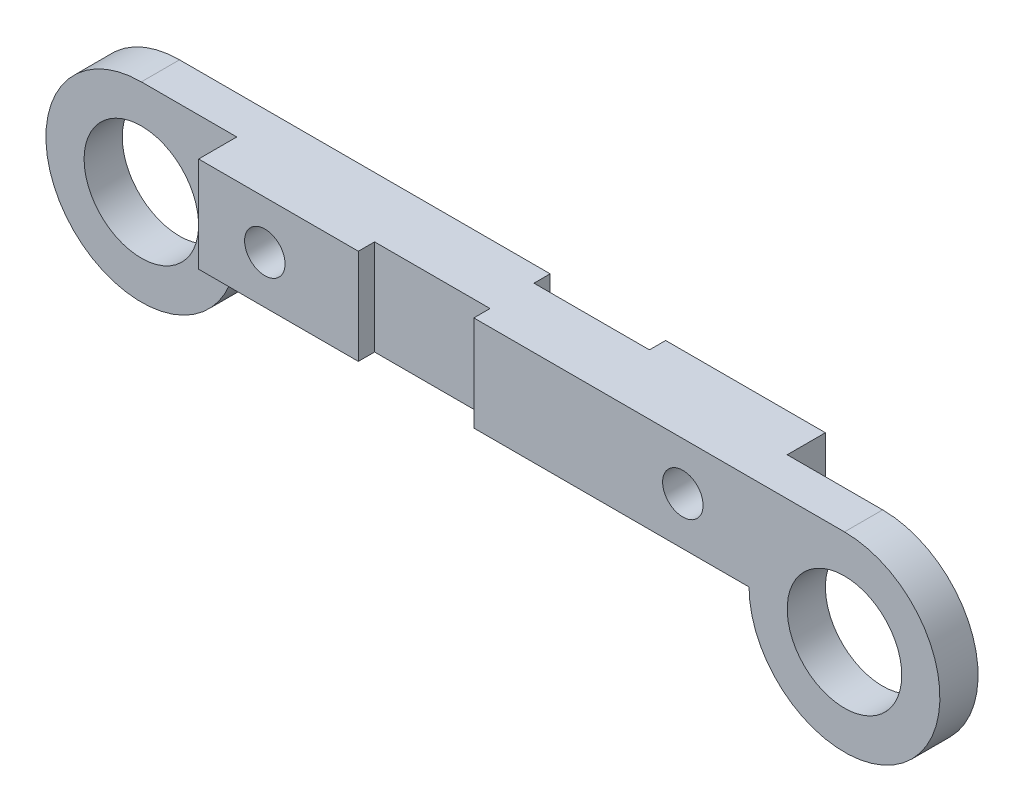
SolidWorks part; units mm, degrees
ref_plane "Front" through (0, 0, 0) normal (0, 0, 1) x (1, 0, 0)
ref_plane "Top" through (0, 0, 0) normal (0, 1, 0) x (1, 0, 0)
ref_plane "Right" through (0, 0, 0) normal (1, 0, 0) x (0, 0, -1)
sketch "Sketch1" plane through (0, 0, 0) normal (0, 0, 1) x (1, 0, 0)
  line L0 (-72.1, -25) -> (72.1, -25)
  line L1 (-97.1, 0) -> (97.1, 0)
  circle A0 centre (-97.1, -25) radius 15
  arc A1 (-97.1, 0) -> (-72.1, -25) centre (-97.1, -25) ccw
  arc A2 (72.1, -25) -> (97.1, 0) centre (97.1, -25) ccw
  circle A3 centre (97.1, -25) radius 15
  dimension "D1" = 50
  dimension "D2" = 30
  dimension "D3" = 30
  dimension "D4" = 194.2
extrude "Boss-Extrude1" add sketch "Sketch1" along normal blind 20
sketch "Sketch2" plane through (0, 0, 0) normal (0, 1, 0) x (1, 0, 0)
  line L8 (72.1, 0) -> (122.1, 0)
  line L9 (72.1, 0) -> (72.1, -10)
  line L10 (-122.1, -10) -> (-72.1, -10)
  line L11 (-122.1, -20) -> (-72.1, -20)
  line L12 (-122.1, -20) -> (-122.1, -10)
  line L13 (72.1, -10) -> (122.1, -10)
  line L14 (-72.1, -20) -> (-72.1, -10)
  line L15 (122.1, 0) -> (122.1, -10)
extrude "Cut-Extrude1" cut sketch "Sketch2" against normal blind 84
sketch "Sketch3" plane through (0, 0, 20) normal (0, 0, 1) x (1, 0, 0)
  line L0 (0, 0) -> (0, -9.9986) construction
  circle A0 centre (-54.755, -12.5) radius 5.2979
  circle A1 centre (54.755, -12.5) radius 5.2979
extrude "Cut-Extrude2" cut sketch "Sketch3" against normal up to surface (20 mm away) up to face at (-13.7944, -20.0444, 0)
sketch "Sketch4" plane through (0, 0, 0) normal (0, 1, 0) x (1, 0, 0)
  line L0 (97.1, -20) -> (-72.1, -20) construction
  line L1 (-30.2527, -20) -> (0, -20)
  line L2 (-30.2527, -20) -> (-30.2527, -15.7505)
  line L3 (-30.2527, -15.7505) -> (0, -15.7505)
  line L4 (0, -20) -> (0, -15.7505)
  line L5 (30.2527, -4.2495) -> (30.2527, 0)
  line L6 (0, 0) -> (30.2527, 0)
  line L7 (0, -4.2495) -> (30.2527, -4.2495)
  line L8 (0, -4.2495) -> (0, 0)
extrude "Cut-Extrude3" cut sketch "Sketch4" against normal blind 31
